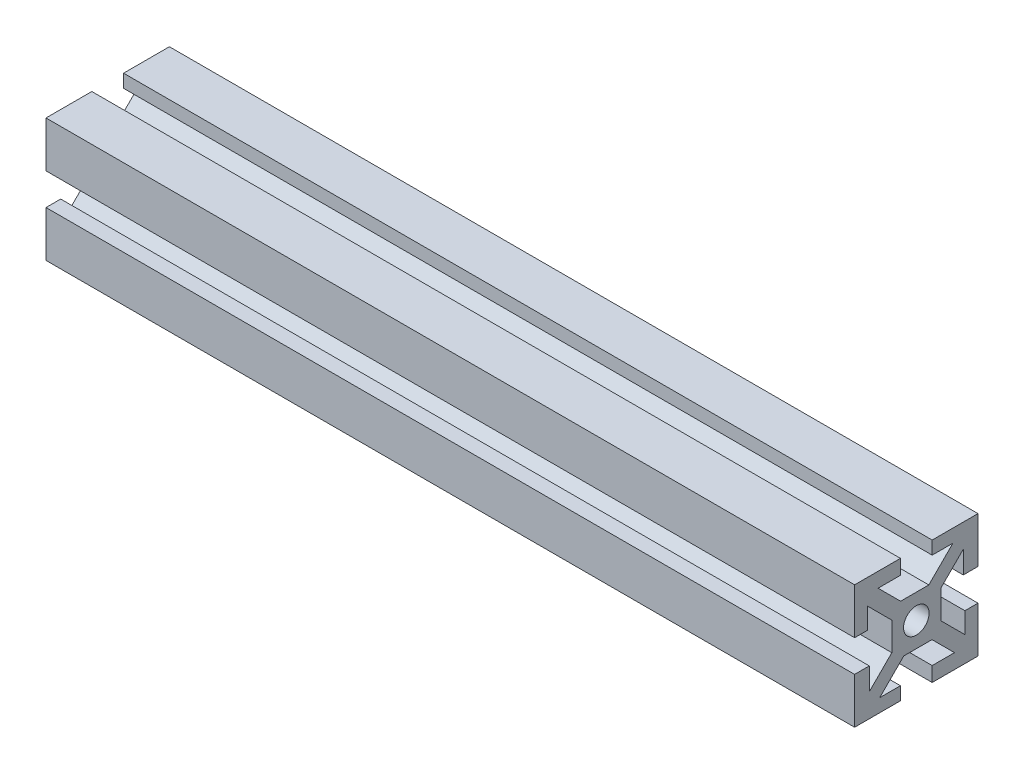
SolidWorks part; units mm, degrees
material "6061 Alloy"
ref_plane "Front Plane" through (0, 0, 0) normal (0, 0, 1) x (1, 0, 0)
ref_plane "Top Plane" through (0, 0, 0) normal (0, 1, 0) x (1, 0, 0)
ref_plane "Right Plane" through (0, 0, 0) normal (1, 0, 0) x (0, 0, -1)
sketch "Sketch1" plane through (0, 0, 0) normal (1, 0, 0) x (0, 0, -1)
  line L0 (2.5534, 5) -> (7.4749, 9.9215)
  line L1 (-5, 5) -> (5, 5)
  line L2 (-5, 5) -> (-5, -5)
  line L3 (-5, -5) -> (5, -5)
  line L4 (5, 5) -> (5, -5)
  line L5 (-5, 5) -> (5, -5) construction
  line L6 (-5, -5) -> (5, 5) construction
  line L7 (7.4749, 9.9215) -> (9.5962, 7.8001)
  line L8 (9.5962, 7.8001) -> (5, 3.2039)
  line L9 (5, 5) -> (13.6489, 13.6489) construction
  line L10 (7.4749, 9.9215) -> (3.24, 9.9215)
  line L11 (3.24, 9.9215) -> (3.24, 12.5962)
  line L12 (3.24, 12.5962) -> (12.5962, 12.5962)
  line L13 (9.5962, 7.8001) -> (9.5962, 3.24)
  line L14 (9.5962, 3.24) -> (12.5962, 3.24)
  line L15 (12.5962, 3.24) -> (12.5962, 12.5962)
  line L17 (0, 0) -> (0, 24.089) construction
  line L18 (0, 0) -> (23.75, 0) construction
  circle A0 centre (0, 0) radius 2.605
  point P0 (0, 0)
  dimension "D1" = 5.21
  dimension "D2" = 10
  dimension "D3" = 10
  dimension "D4" = 3
  dimension "D5" = 1.27
  dimension "D6" = 6.5
  dimension "D7" = 3.24
  dimension "D8" = 3.24
  dimension "D9" = 3
extrude "Boss-Extrude1" add sketch "Sketch1" along normal blind 165.1 contours L4 L1 L2 L3 A0 | L8 L7 L0 L1 L4 | L14 L15 L12 L11 L10 L7 L13 region at (0, 4.8586, -3.7767) region at (0, 6.7479, -6.3823) region at (0, 9.18, -9.3105)
ref_axis "Axis1" through (0, 0, 0) along (1, 0, 0)
pattern_circular "CirPattern1" count 4 over 360 about axis through (0, 0, 0) along (1, 0, 0) of "Boss-Extrude1"
sketch "Sketch2" plane through (0, 0, 12.5962) normal (0, 0, 1) x (1, 0, 0)
  circle A0 centre (86.36, 0) radius 2.38
  dimension "D1" = 4.76
  dimension "D2" = 86.36
extrude "Cut-Extrude6" cut sketch "Sketch2" against normal blind 8
